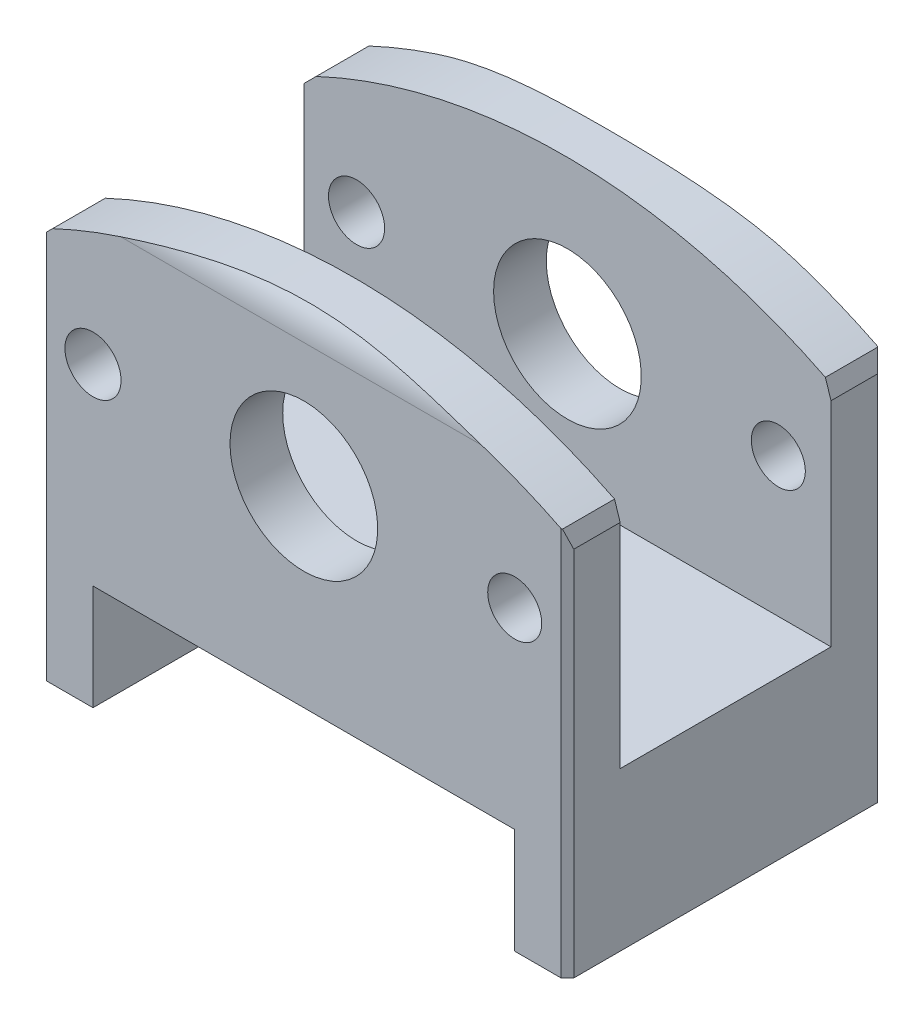
SolidWorks part; units mm, degrees
ref_plane "Front Plane" through (0, 0, 0) normal (0, 0, 1) x (1, 0, 0)
ref_plane "Top Plane" through (0, 0, 0) normal (0, 1, 0) x (1, 0, 0)
ref_plane "Right Plane" through (0, 0, 0) normal (1, 0, 0) x (0, 0, -1)
sketch "Sketch1" plane through (0, 0, 0) normal (0, 0, 1) x (1, 0, 0)
  line L1 (0, 0) -> (63.5, 0)
  line L2 (0, 0) -> (0, 57.15)
  line L3 (0, 57.15) -> (63.5, 57.15)
  line L4 (63.5, 0) -> (63.5, 57.15)
  point P5 (0, 28.575)
  dimension "D1" = 63.5
  dimension "D2" = 57.15
extrude "Boss-Extrude1" add sketch "Sketch1" along normal blind 38.1 contours L4 L3 L2 L1
sketch "Sketch2" plane through (0, 0, 0) normal (0, 0, -1) x (-1, 0, 0)
  line L0 (0, 0) -> (-63.5, 0) construction
  line L1 (-57.15, 12.7) -> (-6.35, 12.7)
  line L2 (-57.15, 12.7) -> (-57.15, 0)
  line L3 (-57.15, 0) -> (-6.35, 0)
  line L4 (-6.35, 12.7) -> (-6.35, 0)
  line L5 (-63.5, 0) -> (-63.5, 57.15) construction
  line L6 (0, 0) -> (0, 57.15) construction
  dimension "D1" = 6.35
  dimension "D2" = 6.35
  dimension "D3" = 12.7
extrude "Cut-Extrude1" cut sketch "Sketch2" against normal through all contours L2 L1 L4 L3
sketch "Sketch3" plane through (0, 57.15, 0) normal (0, 1, 0) x (1, 0, 0)
  line L0 (0, -38.1) -> (0, 0) construction
  line L1 (63.5, -31.75) -> (0, -31.75)
  line L2 (63.5, -31.75) -> (63.5, -6.35)
  line L3 (63.5, -6.35) -> (0, -6.35)
  line L4 (0, -31.75) -> (0, -6.35)
  line L5 (0, -38.1) -> (63.5, -38.1) construction
  dimension "D1" = 25.4
  dimension "D2" = 63.5
  dimension "D3" = 6.35
extrude "Cut-Extrude2" cut sketch "Sketch3" against normal blind 38.1
fillet "Fillet3" radius 6.35 1 edges at (31.75, 57.15, 38.1)
fillet "Fillet4" radius 6.35 1 edges at (31.75, 57.15, 0)
sketch "Sketch4" plane through (0, 0, 0) normal (0, 0, -1) x (-1, 0, 0)
  line L0 (-63.5, 0) -> (-63.5, 50.8) construction
  line L1 (0, 0) -> (0, 50.8) construction
  circle A0 centre (-57.15, 35.8193) radius 3.2527
  circle A1 centre (-6.35, 35.8193) radius 3.3795
  circle A2 centre (-31.75, 35.8193) radius 8.8955
  dimension "D1" = 6.35
  dimension "D2" = 6.35
  dimension "D3" = 31.75
extrude "Cut-Extrude3" cut sketch "Sketch4" against normal through all
chamfer "Chamfer1" distance 0.762 angle 45 2 edges at (63.5, 55.2901, 1.8599) (63.5, 25.4, 0)
chamfer "Chamfer2" distance 0.762 angle 45 6 edges at (63.5, 55.2901, 36.2401) (63.5, 25.4, 38.1) (0, 55.2901, 36.2401) (0, 25.4, 38.1) (0, 55.2901, 1.8599) (0, 25.4, 0)
sketch "Sketch5" plane through (0, 0, 31.75) normal (0, 0, -1) x (-1, 0, 0)
  arc A0 (1.8392, 45.8709) -> (-67.0987, 44.503) centre (-31.4169, -15.9328) ccw
  point P3 (-63.2657, 50.9717)
  point P4 (0, 50.9512)
  point P5 (0, 0)
  point P6 (0, 0)
  point P7 (0, 0)
  point P8 (-63.7268, 45.3959)
  point P9 (-1.7611, 45.3959)
  point P10 (5.8272, 43.832)
  point P11 (-69.246, 43.832)
  point P12 (0, 0)
  point P13 (0, 0)
  point P14 (1.8392, 45.8709)
  point P15 (0, 0)
  point P16 (-67.0987, 44.503)
extrude "Cut-Extrude5" cut sketch "Sketch5" against normal through all and the other way through all flip side to cut
chamfer "Chamfer3" distance 0.762 angle 45 4 edges at (0, 46.8258, 3.556) (0, 46.8258, 34.544) (63.5, 46.4879, 3.556) (63.5, 46.4879, 34.544) first distance on face at (0, 28.1754, 19.05) first distance on face at (32.8357, 49.1324, 1.8614) first distance on face at (30.5106, 49.1324, 36.2386)
